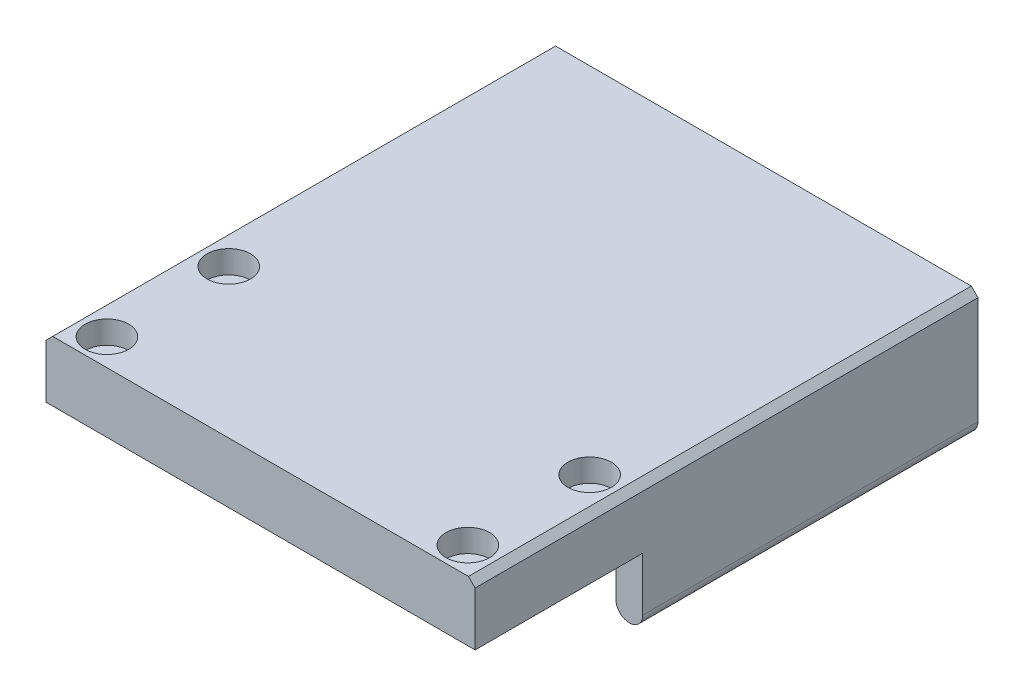
SolidWorks part; units mm, degrees
ref_plane "Front Plane" through (0, 0, 0) normal (0, 0, 1) x (1, 0, 0)
ref_plane "Top Plane" through (0, 0, 0) normal (0, 1, 0) x (1, 0, 0)
ref_plane "Right Plane" through (0, 0, 0) normal (1, 0, 0) x (0, 0, -1)
sketch "Sketch1" plane through (0, 0, 0) normal (0, 1, 0) x (1, 0, 0)
  line L0 (32, -75) -> (-32, -75)
  line L1 (0, -75) -> (0, -150) construction
  line L2 (32, -150) -> (-32, -150)
  line L3 (-32, -150) -> (-32, -75)
  line L4 (32, -150) -> (32, -75)
  dimension "\"neck length" = 75
extrude "Boss-Extrude1" add sketch "Sketch1" along normal blind 19
shell "Shell1" thickness 4 removed face at (0, 0, 112.5)
fillet "Fillet2" 2 edges at (32, 0, 112.5) (28, 0, 112.5) type full round first side face at (32, 9.5, 112.5) second side face at (28, 5, 112.5) middle face at (0, 0, 112.5)
fillet "Fillet3" 2 edges at (-32, 0, 112.5) (-28, 0, 112.5) type full round first side face at (-32, 9.5, 112.5) second side face at (-28, 5, 112.5) middle face at (0, 0, 112.5)
chamfer "Chamfer1" distance 1 angle 45 2 edges at (32, 19, 112.5) (-32, 19, 112.5)
sketch "Sketch7" plane through (0, 0, 150) normal (0, 0, 1) x (1, 0, 0)
  line L1 (-32, 10) -> (32, 10)
  line L2 (-32, 18) -> (-32, 2) construction
  line L3 (32, 18) -> (32, 2) construction
  line L4 (32, 10) -> (32, 0)
  line L7 (-32, 0) -> (-32, 10)
  line L8 (-32, 0) -> (32, 0)
extrude "Cut-Extrude3" cut sketch "Sketch7" against normal blind 25
hole_wizard "CBORE for M3 Hex Socket Head Cap Screw1" positions "Sketch12" profile "Sketch13" counterbore size "M3" standard "ISO" end condition through all
sketch "Sketch12" plane through (75.2969, 19, 61.2992) normal (0, 1, 0) x (1, 0, 0)
  point P0 (-102.2096, -66.5318)
  point P1 (-102.2096, -84.7008)
  point P2 (-48.3841, -84.7008)
  point P3 (-48.3841, -66.5318)
sketch "Sketch13" plane through (-26.9127, 19, 127.831) normal (1, 0, 0) x (0, 0, 1)
  line L0 (0, 0) -> (0, 19)
  line L1 (0, 19) -> (1.45, 19)
  line L2 (1.45, 19) -> (1.45, 3.4)
  line L3 (1.45, 3.4) -> (3.25, 3.4)
  line L4 (3.25, 3.4) -> (3.25, 0)
  line L5 (3.25, 0) -> (0, 0)
  line L6 (0, -6.35) -> (0, 107.95) construction
  dimension "Thru Hole Dia." = 2.9
  dimension "Thru Hole Depth" = 19
  dimension "C'Bore Dia." = 6.5
  dimension "C'Bore Depth" = 3.4
ref_plane "Plane1" through (0, 0, 100) normal (0, 0, 1) x (1, 0, 0)
equation "\"neck length\"= 200mm"
equation "\"stringLength\"=69.2489"
